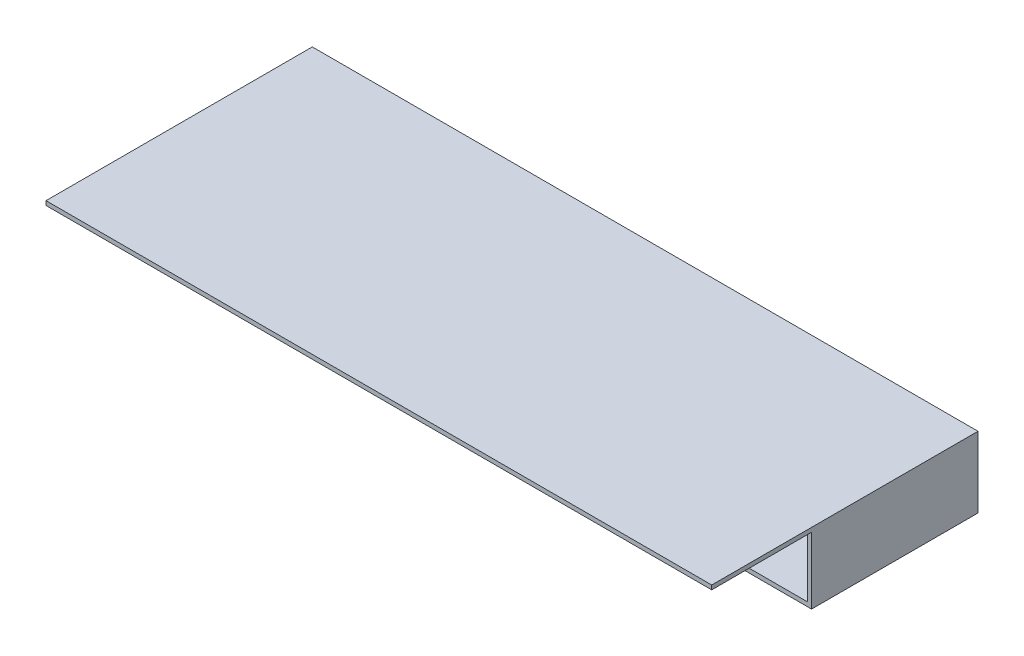
SolidWorks part; units mm, degrees
ref_plane "Front Plane" through (0, 0, 0) normal (0, 0, 1) x (1, 0, 0)
ref_plane "Top Plane" through (0, 0, 0) normal (0, 1, 0) x (1, 0, 0)
ref_plane "Right Plane" through (0, 0, 0) normal (1, 0, 0) x (0, 0, -1)
sketch "Sketch1" plane through (0, 0, 0) normal (0, 1, 0) x (1, 0, 0)
  line L1 (1000, -400) -> (-1000, -400)
  line L2 (1000, -400) -> (1000, 400)
  line L3 (1000, 400) -> (-1000, 400)
  line L4 (-1000, -400) -> (-1000, 400)
  line L5 (1000, -400) -> (-1000, 400) construction
  line L6 (1000, 400) -> (-1000, -400) construction
  point P0 (0, 0)
  dimension "D1" = 2000
  dimension "D2" = 800
extrude "Boss-Extrude1" add sketch "Sketch1" along normal blind 12.7 contours L4 L3 L2 L1
sketch "Sketch2" plane through (0, 0, 0) normal (0, -1, 0) x (1, 0, 0)
  line L0 (1000, 400) -> (1000, -400) construction
  line L1 (-1000, -400) -> (1000, -400)
  line L2 (-1000, -400) -> (-1000, 100)
  line L3 (-1000, 100) -> (1000, 100)
  line L4 (1000, -400) -> (1000, 100)
  dimension "D1" = 500
extrude "Boss-Extrude2" add sketch "Sketch2" along normal blind 200
shell "Shell1" thickness 12.7 removed face at (0, -100, 100)
sketch "Sketch4" plane through (0, 0, -387.3) normal (0, 0, 1) x (1, 0, 0)
  line L0 (0, 0) -> (0, -187.3) construction
  line L1 (987.3, -187.3) -> (-987.3, -187.3) construction
  line L2 (987.3, 0) -> (-987.3, 0) construction
  line L3 (12.7, -187.3) -> (-12.7, -187.3)
  line L4 (12.7, -187.3) -> (12.7, 0)
  line L5 (12.7, 0) -> (-12.7, 0)
  line L6 (-12.7, -187.3) -> (-12.7, 0)
  line L7 (12.7, -187.3) -> (-12.7, 0) construction
  line L8 (12.7, 0) -> (-12.7, -187.3) construction
  point P5 (0, -93.65)
  dimension "D1" = 25.4
extrude "Boss-Extrude3" add sketch "Sketch4" along normal up to surface (487.3 mm away) up to face at (0, -96.825, 100)
